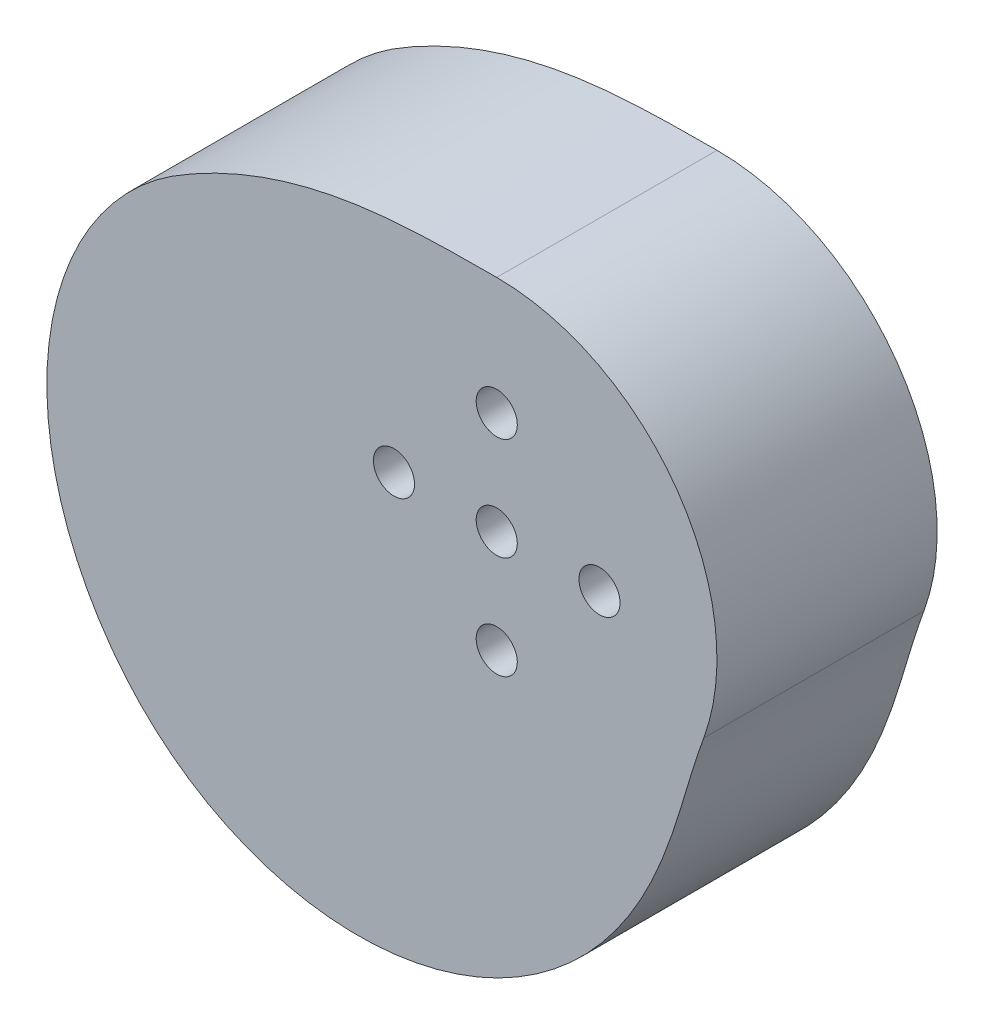
SolidWorks part; units mm, degrees
ref_plane "前视基准面" through (0, 0, 0) normal (0, 0, 1) x (1, 0, 0)
ref_plane "上视基准面" through (0, 0, 0) normal (0, 1, 0) x (1, 0, 0)
ref_plane "右视基准面" through (0, 0, 0) normal (1, 0, 0) x (0, 0, -1)
ref_axis "基准轴1" through (0, 0, -88.99) along (0, 0, 1)
sketch "草图1" plane through (0, 0, 0) normal (0, 0, 1) x (1, 0, 0)
  arc A0 (14.0954, -5.1303) -> (0, 15) centre (0, 0) ccw
  spline S0 degree 3 poles (0, 15) (-0.1746, 15) (-0.4366, 14.9997) (-0.7862, 14.9986) (-1.0489, 14.9975) (-1.3122, 14.996) (-1.5762, 14.9942) (-1.8411, 14.9919) (-2.1069, 14.9891) (-2.3739, 14.9858) (-2.6422, 14.982) (-2.9118, 14.9775) (-3.183, 14.9724) (-3.4559, 14.9664) (-3.7305, 14.9597) (-4.007, 14.952) (-4.2856, 14.9433) (-4.5663, 14.9335) (-4.8494, 14.9224) (-5.1347, 14.9101) (-5.4226, 14.8963) (-5.7131, 14.8809) (-6.0063, 14.8639) (-6.3023, 14.8451) (-6.6012, 14.8243) (-6.903, 14.8015) (-7.208, 14.7764) (-7.516, 14.749) (-7.8273, 14.7191) (-8.1419, 14.6864) (-8.4599, 14.651) (-8.7812, 14.6125) (-9.1061, 14.5709) (-9.4344, 14.5259) (-9.7663, 14.4774) (-10.1018, 14.4251) (-10.441, 14.369) (-10.7838, 14.3088) (-11.1303, 14.2444) (-11.4804, 14.1755) (-11.8343, 14.1019) (-12.1918, 14.0235) (-12.553, 13.94) (-12.9179, 13.8512) (-13.2864, 13.757) (-13.6586, 13.6571) (-14.0343, 13.5513) (-14.4136, 13.4395) (-14.7964, 13.3213) (-15.1826, 13.1966) (-15.5722, 13.0652) (-15.9651, 12.9269) (-16.3612, 12.7814) (-16.7604, 12.6285) (-17.1627, 12.4681) (-17.5679, 12.2999) (-17.9759, 12.1236) (-18.3867, 11.9392) (-18.8, 11.7463) (-19.2158, 11.5448) (-19.634, 11.3344) (-20.0542, 11.115) (-20.4765, 10.8864) (-20.9007, 10.6483) (-21.3265, 10.4003) (-21.7535, 10.1438) (-22.178, 9.8754) (-22.596, 9.5923) (-23.0069, 9.2962) (-23.4102, 8.9872) (-23.8057, 8.6654) (-24.193, 8.3311) (-24.5718, 7.9846) (-24.9417, 7.6261) (-25.3024, 7.256) (-25.6535, 6.8745) (-25.9949, 6.4818) (-26.3262, 6.0784) (-26.647, 5.6645) (-26.9572, 5.2405) (-27.2565, 4.8065) (-27.5445, 4.3631) (-27.8211, 3.9104) (-28.0859, 3.4489) (-28.3389, 2.9789) (-28.5796, 2.5008) (-28.8081, 2.0148) (-29.0239, 1.5214) (-29.227, 1.0209) (-29.4171, 0.5138) (-29.5942, 0.0003) (-29.7579, -0.5192) (-29.9082, -1.0442) (-30.045, -1.5744) (-30.1681, -2.1093) (-30.2773, -2.6487) (-30.3727, -3.1921) (-30.454, -3.7391) (-30.5212, -4.2893) (-30.5742, -4.8423) (-30.613, -5.3977) (-30.6375, -5.9552) (-30.6477, -6.5142) (-30.6435, -7.0745) (-30.6249, -7.6355) (-30.5919, -8.197) (-30.5445, -8.7584) (-30.4828, -9.3194) (-30.4066, -9.8796) (-30.3162, -10.4386) (-30.2115, -10.996) (-30.0925, -11.5513) (-29.9594, -12.1043) (-29.8122, -12.6545) (-29.651, -13.2014) (-29.476, -13.7448) (-29.2871, -14.2842) (-29.0846, -14.8193) (-28.8686, -15.3496) (-28.6391, -15.8749) (-28.3964, -16.3947) (-28.1407, -16.9086) (-27.872, -17.4163) (-27.5906, -17.9175) (-27.2967, -18.4118) (-26.9904, -18.8988) (-26.6719, -19.3783) (-26.3416, -19.8498) (-25.8855, -20.4675) (-25.5263, -20.9179) (-25.2795, -21.212) knots 0 0 0 0 0.008984 0.013482 0.017987 0.022502 0.027029 0.031572 0.036131 0.040709 0.04531 0.049934 0.054586 0.059265 0.063976 0.068721 0.0735 0.078317 0.083174 0.088073 0.093015 0.098004 0.10304 0.108126 0.113264 0.118455 0.123702 0.129006 0.134369 0.139793 0.14528 0.15083 0.156446 0.16213 0.167883 0.173706 0.179601 0.18557 0.191613 0.197734 0.203932 0.210209 0.216567 0.223007 0.229531 0.236139 0.242833 0.249615 0.256485 0.263445 0.270496 0.277639 0.284876 0.292207 0.299634 0.307159 0.314781 0.322503 0.330326 0.33825 0.346277 0.354408 0.362644 0.370986 0.379435 0.387993 0.396619 0.405275 0.41396 0.422674 0.431418 0.440191 0.448994 0.457827 0.46669 0.475583 0.484505 0.493456 0.502437 0.511447 0.520487 0.529555 0.538652 0.547777 0.55693 0.566111 0.57532 0.584555 0.593818 0.603106 0.612421 0.621761 0.631127 0.640517 0.649931 0.659369 0.66883 0.678314 0.68782 0.697347 0.706896 0.716465 0.726054 0.735662 0.745289 0.754934 0.764597 0.774276 0.783972 0.793683 0.803409 0.81315 0.822904 0.83267 0.842449 0.85224 0.862041 0.871853 0.881674 0.891504 0.901341 0.911186 0.921038 0.930895 0.940758 0.950625 0.960495 0.970369 0.980245 1 1 1 1
  spline S1 degree 3 poles (-25.2795, -21.212) (-25.0327, -21.5061) (-24.6501, -21.9369) (-24.1163, -22.4889) (-23.7046, -22.8914) (-23.2819, -23.282) (-22.8486, -23.6605) (-22.4049, -24.0265) (-21.9514, -24.3797) (-21.4885, -24.7199) (-21.0165, -25.0467) (-20.5359, -25.36) (-20.0471, -25.6594) (-19.5507, -25.9449) (-19.047, -26.2162) (-18.5364, -26.4731) (-18.0196, -26.7155) (-17.4968, -26.9432) (-16.9687, -27.156) (-16.4357, -27.354) (-15.8982, -27.537) (-15.3568, -27.7049) (-14.8119, -27.8577) (-14.264, -27.9953) (-13.7136, -28.1177) (-13.1612, -28.225) (-12.6073, -28.3171) (-12.0523, -28.3942) (-11.4967, -28.4561) (-10.941, -28.5031) (-10.3857, -28.5352) (-9.8311, -28.5525) (-9.2779, -28.5552) (-8.7263, -28.5434) (-8.1769, -28.5172) (-7.6301, -28.4768) (-7.0863, -28.4224) (-6.5459, -28.3543) (-6.0093, -28.2726) (-5.4769, -28.1775) (-4.9492, -28.0694) (-4.4264, -27.9484) (-3.909, -27.8149) (-3.3972, -27.6692) (-2.8914, -27.5114) (-2.392, -27.342) (-1.8992, -27.1613) (-1.4133, -26.9695) (-0.9346, -26.7671) (-0.4634, -26.5543) (0, -26.3316) (0.4556, -26.0993) (0.903, -25.8577) (1.342, -25.6072) (1.7725, -25.3482) (2.1942, -25.0811) (2.6072, -24.8063) (3.0111, -24.5241) (3.4059, -24.235) (3.7915, -23.9393) (4.1677, -23.6375) (4.5346, -23.3299) (4.8921, -23.0169) (5.2402, -22.6989) (5.5787, -22.3763) (5.9078, -22.0495) (6.2274, -21.7189) (6.5376, -21.3849) (6.8384, -21.0477) (7.1298, -20.7079) (7.412, -20.3657) (7.685, -20.0215) (7.9489, -19.6757) (8.2039, -19.3286) (8.45, -18.9805) (8.6875, -18.6318) (8.9164, -18.2828) (9.1369, -17.9338) (9.3493, -17.585) (9.5536, -17.2367) (9.7501, -16.8893) (9.9391, -16.543) (10.1206, -16.1981) (10.2951, -15.8546) (10.4626, -15.513) (10.6234, -15.1734) (10.7778, -14.836) (10.926, -14.5009) (11.0683, -14.1684) (11.2049, -13.8386) (11.3362, -13.5116) (11.4624, -13.1876) (11.5837, -12.8667) (11.7005, -12.5489) (11.8131, -12.2344) (11.9216, -11.9232) (12.0264, -11.6154) (12.1278, -11.3109) (12.226, -11.0099) (12.3214, -10.7123) (12.4141, -10.4182) (12.5046, -10.1274) (12.5929, -9.8401) (12.6795, -9.556) (12.7645, -9.2752) (12.8482, -8.9976) (12.9308, -8.7232) (13.0127, -8.4517) (13.0939, -8.1831) (13.1748, -7.9172) (13.2556, -7.654) (13.3364, -7.3933) (13.4175, -7.135) (13.499, -6.8788) (13.5811, -6.6245) (13.664, -6.3721) (13.7479, -6.1213) (13.8328, -5.872) (13.9475, -5.5413) (14.0357, -5.2944) (14.0954, -5.1303) knots 0 0 0 0 0.02127 0.031904 0.042535 0.053163 0.063787 0.074406 0.08502 0.095628 0.106228 0.116821 0.127405 0.13798 0.148544 0.159097 0.169638 0.180166 0.19068 0.20118 0.211663 0.22213 0.23258 0.243011 0.253422 0.263812 0.274181 0.284528 0.29485 0.305148 0.31542 0.325664 0.335881 0.346068 0.356224 0.366349 0.376441 0.386499 0.396521 0.406507 0.416454 0.426363 0.436231 0.446057 0.45584 0.465578 0.475271 0.484916 0.494513 0.50406 0.513556 0.522999 0.532388 0.541722 0.550999 0.560217 0.569377 0.578475 0.587511 0.596484 0.605392 0.614233 0.623007 0.631713 0.640348 0.648912 0.657404 0.665822 0.674165 0.682432 0.690623 0.698735 0.706768 0.714721 0.722594 0.730384 0.738092 0.745717 0.753257 0.760713 0.768084 0.775369 0.782568 0.78968 0.796706 0.803645 0.810497 0.817263 0.823941 0.830534 0.83704 0.843461 0.849797 0.856048 0.862216 0.868302 0.874307 0.880232 0.886079 0.891849 0.897544 0.903166 0.908717 0.9142 0.919616 0.92497 0.930262 0.935498 0.940679 0.945809 0.950892 0.955931 0.96093 0.965894 0.970826 0.97573 0.980612 0.985475 0.990325 1 1 1 1
extrude "凸台-拉伸1" add sketch "草图1" along normal blind 15
sketch "草图2" plane through (0, 0, 0) normal (0, 0, 1) x (1, 0, 0)
  line L0 (0.9848, -0.1736) -> (0.6375, -2.1433)
  line L1 (0.6375, -2.1433) -> (-1.3321, -1.796)
  line L2 (-1.3321, -1.796) -> (-0.9848, 0.1736)
  arc A0 (0.9848, -0.1736) -> (-0.9848, 0.1736) centre (0, 0) ccw
extrude "切除-拉伸1" [suppressed] cut sketch "草图2" against normal blind 10 and the other way blind 10
sketch "草图3" plane through (0, 0, 15) normal (0, 0, 1) x (1, 0, 0)
  line L0 (7, 0) -> (0, 0) construction
  circle A0 centre (0, 0) radius 1.4
  circle A1 centre (7, 0) radius 1.4
  circle A2 centre (0, -7) radius 1.4
  circle A3 centre (-7, 0) radius 1.4
  circle A4 centre (0, 7) radius 1.4
  point P13 (0, 0)
  dimension "D1" = 2.8
  dimension "D2" = 2.8
  dimension "D3" = 7
  dimension "D4" = 4
extrude "切除-拉伸2" cut sketch "草图3" against normal through all
